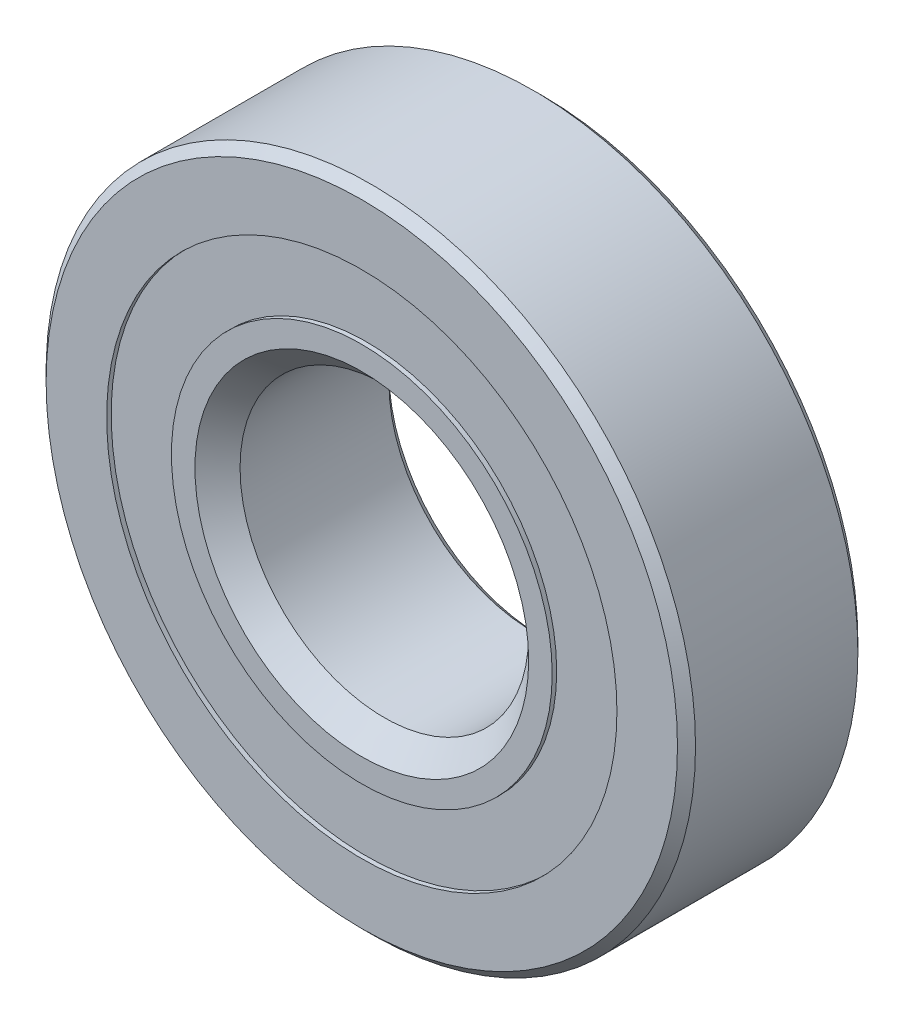
SolidWorks part; units mm, degrees
ref_plane "Front Plane" through (0, 0, 0) normal (0, 0, 1) x (1, 0, 0)
ref_plane "Top Plane" through (0, 0, 0) normal (0, 1, 0) x (1, 0, 0)
ref_plane "Right Plane" through (0, 0, 0) normal (1, 0, 0) x (0, 0, -1)
sketch "Sketch1" plane through (0, 0, 0) normal (1, 0, 0) x (0, 0, -1)
  line L0 (-3.9688, 0) -> (3.9688, 0) construction
  line L1 (0, 14.2875) -> (0, -14.2875) construction
  line L2 (3.5719, 14.2875) -> (-3.5719, 14.2875)
  line L3 (-3.5719, 14.2875) -> (-3.9688, 13.8906)
  line L4 (-3.9688, 13.8906) -> (-3.9688, 11.2259)
  line L5 (-3.9688, 11.2259) -> (-1.7639, 11.2259)
  line L6 (3.9688, 11.2259) -> (1.7639, 11.2259)
  line L7 (3.9688, 13.8906) -> (3.9688, 11.2259)
  line L8 (3.5719, 14.2875) -> (3.9688, 13.8906)
  line L9 (0, 14.2875) -> (0, 10.3187) construction
  line L10 (0, 10.3187) -> (0, 6.35) construction
  arc A0 (-1.7639, 11.2259) -> (1.7639, 11.2259) centre (0, 10.3187) cw
  point P14 (0, 6.35)
  dimension "Width" = 7.9375
  dimension "OD" = 28.575
  dimension "D1" = 45
  dimension "D2" = 0.3969
  dimension "D3" = 3.5278
  dimension "D4" = 0.9071
revolve "Revolve1" add sketch "Sketch1" angle 360 about L0
sketch "Sketch2" plane through (0, 0, 0) normal (1, 0, 0) x (0, 0, -1)
  line L0 (-3.7703, 9.4116) -> (-1.7639, 9.4116)
  line L1 (-3.9688, 13.8906) -> (-3.9688, -13.8906) construction
  line L2 (-3.9688, 8.3771) -> (-3.7703, 8.3771) construction
  line L3 (-3.7703, 8.1787) -> (-2.9343, 7.3426)
  line L4 (-2.9343, 7.3426) -> (0, 7.3426)
  line L5 (0, 14.2875) -> (0, -14.2875) construction
  line L6 (0, 7.3426) -> (0, 8.3353)
  line L7 (0, 8.3353) -> (0, 6.35) construction
  line L8 (-3.9688, 9.4116) -> (-3.9688, 7.3426) construction
  line L9 (-3.9688, 7.3426) -> (-2.9343, 7.3426) construction
  line L10 (-3.7703, 9.4116) -> (-3.7703, 8.1787)
  line L11 (-3.7703, 9.4116) -> (-3.7703, 14.0891) construction
  line L12 (-3.5719, 14.2875) -> (-3.9688, 13.8906) construction
  arc A0 (-1.7639, 9.4116) -> (0, 8.3353) centre (0, 10.3187) ccw
  arc A1 (1.7639, 11.2259) -> (-1.7639, 11.2259) centre (0, 10.3187) ccw construction
  circle A2 centre (0, 10.3187) radius 1.9835 construction
  dimension "D1" = 45
revolve "Revolve2" [suppressed] add sketch "Sketch2" angle 360 about L0
sketch "Sketch3" plane through (0, 0, 0) normal (1, 0, 0) x (0, 0, -1)
  line L0 (-3.7703, 8.1787) -> (-2.9343, 7.3426)
  line L1 (-2.9343, 7.3426) -> (0, 7.3426)
  line L2 (0, 7.3426) -> (0, 8.3353)
  line L3 (-3.9688, 8.3771) -> (-3.9688, 7.3426)
  line L4 (-3.9688, 9.4116) -> (-3.9688, 7.3426) construction
  line L5 (-3.9688, 7.3426) -> (-2.9761, 6.35)
  line L6 (-2.9761, 6.35) -> (3.5719, 6.35)
  line L7 (3.5719, 14.2875) -> (3.5719, -14.2875) construction
  line L8 (3.5719, 6.35) -> (3.9688, 6.7469)
  line L9 (3.9688, -13.8906) -> (3.9688, 13.8906) construction
  line L10 (3.9688, 6.7469) -> (3.9688, 9.4116)
  line L11 (3.9688, 9.4116) -> (1.7639, 9.4116)
  line L12 (-3.9688, 8.3771) -> (-3.7703, 8.3771)
  line L13 (3.5719, 14.2875) -> (3.9688, 13.8906) construction
  line L14 (-3.7703, 8.3771) -> (-3.7703, 8.1787)
  circle A0 centre (0, 10.3187) radius 1.9835 construction
  arc A1 (1.7639, 9.4116) -> (0, 8.3353) centre (0, 10.3187) cw
revolve "Revolve3" add sketch "Sketch3" angle 360 about L0
sketch "Sketch4" plane through (0, 0, 0) normal (1, 0, 0) x (0, 0, -1)
  line L0 (-1.9835, 10.3187) -> (1.9835, 10.3187)
  circle A1 centre (0, 10.3187) radius 1.9835 construction
  arc A2 (-1.9835, 10.3187) -> (1.9835, 10.3187) centre (0, 10.3187) cw
  arc A3 (1.7639, 11.2259) -> (-1.7639, 11.2259) centre (0, 10.3187) ccw construction
revolve "Revolve4" add sketch "Sketch4" angle 360 about L0
ref_axis "Axis1" through (0, 0, -3.9688) along (0, 0, 1)
pattern_circular "CirPattern1" count 12 every 30 about axis through (0, 0, -3.9688) along (0, 0, 1) of bodies 104
sketch "Sketch5" plane through (0, 0, 0) normal (1, 0, 0) x (0, 0, -1)
  line L0 (-3.9688, 11.2259) -> (-1.7639, 11.2259) construction
  line L1 (-3.7703, 11.2259) -> (-1.9835, 11.2259)
  line L2 (-3.7703, 11.2259) -> (-3.7703, 8.3771)
  line L3 (-3.7703, 8.3771) -> (-1.9835, 8.3771)
  line L4 (-1.9835, 11.2259) -> (-1.9835, 8.3771)
  line L6 (-3.5719, 14.2875) -> (-3.9688, 13.8906) construction
  line L7 (0, 14.2875) -> (0, 6.35) construction
  line L8 (3.7703, 8.3771) -> (1.9835, 8.3771)
  line L9 (1.9835, 11.2259) -> (1.9835, 8.3771)
  line L10 (3.7703, 11.2259) -> (1.9835, 11.2259)
  line L11 (3.7703, 11.2259) -> (3.7703, 8.3771)
  circle A0 centre (0, 10.3187) radius 1.9835 construction
  point P10 (-3.7703, 14.0891)
revolve "Revolve5" add sketch "Sketch5" angle 360 about L0
equation "\"D2@Sketch1\" = \"Width@Sketch1\"*.05"
equation "\"D3@Sketch1\" = \"Width@Sketch1\"/2.25"
equation "\"D4@Sketch1\" = (((\"OD@Sketch1\"-\"Width@Sketch1\")/2)/3.25)/3.5"
equation "\"D2@CirPattern1\" = 360/\"Balls@CirPattern1\""
